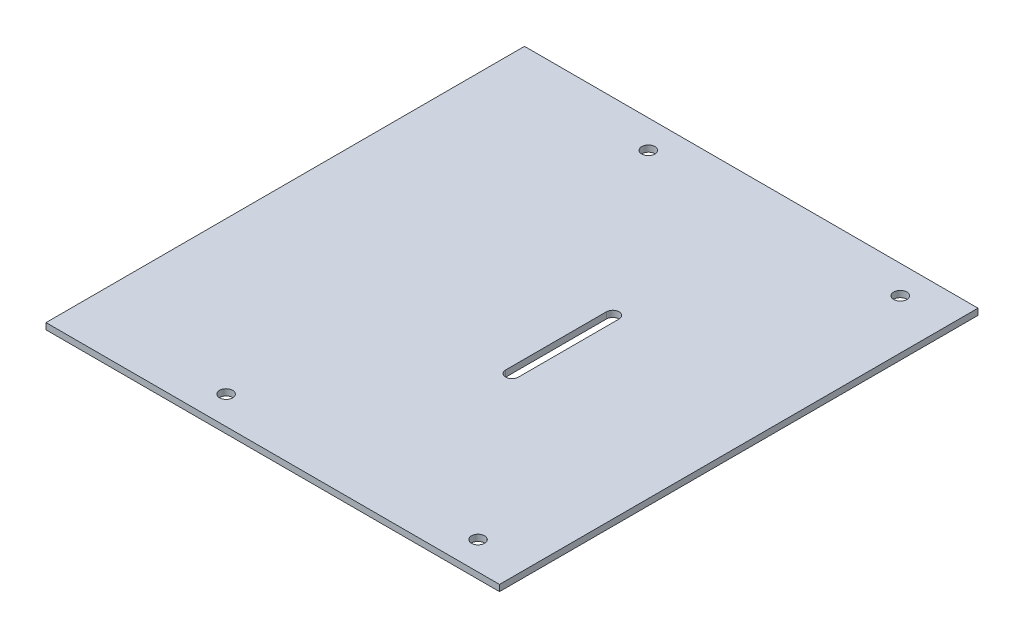
SolidWorks part; units mm, degrees
material "1060 Alloy"
ref_plane "Front Plane" through (0, 0, 0) normal (0, 0, 1) x (1, 0, 0)
ref_plane "Top Plane" through (0, 0, 0) normal (0, 1, 0) x (1, 0, 0)
ref_plane "Right Plane" through (0, 0, 0) normal (1, 0, 0) x (0, 0, -1)
sketch "Sketch1" plane through (0, 0, 0) normal (0, 1, 0) x (1, 0, 0)
  line L0 (361.95, 119.6) -> (-361.95, 119.6) construction
  line L1 (-140.35, -120.6) -> (-368.95, -120.6)
  line L2 (-140.35, -120.6) -> (-140.35, 120.6)
  line L3 (-140.35, 120.6) -> (-368.95, 120.6)
  line L4 (-368.95, -120.6) -> (-368.95, 120.6)
  line L5 (0, -3.8154) -> (0, 119.6) construction
  line L6 (361.3726, 120.6) -> (-361.3726, 120.6) construction
  line L7 (361.3726, -120.6) -> (-361.3726, -120.6) construction
  point P0 (0, 0)
  point P7 (-140.35, 0)
  dimension "D2" = 737.9
  dimension "D3" = 228.6
  dimension "D1" = 241.2
extrude "Boss-Extrude1" add sketch "Sketch1" along normal mid plane 3.175
hole_wizard "M6 Clearance Hole1" positions "Sketch8" profile "Sketch3" hole size "M6" standard "ANSI Metric" end condition through all
sketch "Sketch8" plane through (0, 1.5875, 0) normal (0, 1, 0) x (1, 0, 0)
  line L0 (-165.35, 106.425) -> (-165.35, -106.425) construction
  line L1 (-165.35, -106.425) -> (-292.35, -106.425) construction
  line L3 (-140.35, -120.6) -> (-140.35, 120.6) construction
  point P0 (-292.35, 106.425)
  point P2 (-165.35, 106.425)
  point P4 (-165.35, -106.425)
  point P6 (-292.35, -106.425)
  point P15 (-165.35, 0)
  dimension "D1" = 212.85
  dimension "D2" = 25
  dimension "D3" = 127
sketch "Sketch3" plane through (-292.35, 1.5875, -106.425) normal (1, 0, 0) x (0, 0, 1)
  line L0 (0, 0) -> (0, 3.175)
  line L1 (0, 3.175) -> (3.3, 3.175)
  line L2 (3.3, 3.175) -> (3.3, 0)
  line L5 (3.3, 0) -> (0, 0)
  line L11 (0, -6.35) -> (0, 107.95) construction
  dimension "Thru Hole Dia." = 6.6
  dimension "Thru Hole Depth" = 3.175
sketch "Sketch5" plane through (0, -1.5875, 0) normal (0, -1, 0) x (1, 0, 0)
  line L0 (-175.95, -92.25) -> (-368.95, -92.25)
  line L3 (-368.95, 92.25) -> (-175.95, 92.25)
  line L5 (-368.95, 120.6) -> (-140.35, 120.6) construction
  line L12 (-368.95, -120.6) -> (-368.95, 120.6) construction
  line L16 (-175.95, 92.25) -> (-175.95, -92.25)
  circle A0 centre (-165.35, 106.425) radius 3.3 construction
  circle A1 centre (-165.35, -106.425) radius 3.3 construction
  dimension "D1" = 14.175
  dimension "D2" = 14.175
  dimension "D3" = 14.175
  dimension "D4" = 193
split "Split1" [suppressed] bodies to split 102
sketch "Sketch6" [suppressed] plane through (0, 1.5875, 0) normal (0, 1, 0) x (1, 0, 0)
  line L0 (-140.35, 120.6) -> (-368.95, 120.6) construction
  line L1 (-217.15, -62.5) -> (-292.15, -62.5)
  line L2 (-217.15, -62.5) -> (-217.15, 62.5)
  line L3 (-217.15, 62.5) -> (-292.15, 62.5)
  line L4 (-292.15, -62.5) -> (-292.15, 62.5)
  line L5 (-217.15, -62.5) -> (-292.15, 62.5) construction
  line L6 (-217.15, 62.5) -> (-292.15, -62.5) construction
  point P0 (-254.65, 0)
  point P10 (-254.65, 120.6)
  dimension "D1" = 125
  dimension "D2" = 75
split "Split2" [suppressed] bodies to split 103 104
sketch "Sketch7" plane through (0, 1.5875, 0) normal (0, 1, 0) x (1, 0, 0)
  line L0 (-229.25, -25.4) -> (-229.25, 25.4) construction
  line L1 (-232.425, -25.4) -> (-232.425, 25.4)
  line L2 (-226.075, -25.4) -> (-226.075, 25.4)
  line L5 (-140.35, -120.6) -> (-140.35, 120.6) construction
  arc A0 (-232.425, -25.4) -> (-226.075, -25.4) centre (-229.25, -25.4) ccw
  arc A1 (-226.075, 25.4) -> (-232.425, 25.4) centre (-229.25, 25.4) ccw
  point P2 (-229.25, 0)
  dimension "D1" = 3.175
  dimension "D2" = 50.8
  dimension "D3" = 88.9
extrude "Cut-Extrude1" [suppressed] cut sketch "Sketch7" against normal up to next
sketch "Sketch9" plane through (0, 1.5875, 0) normal (0, 1, 0) x (1, 0, 0)
  line L2 (-226.075, -25.4) -> (-226.075, 25.4)
  line L3 (-232.425, 25.4) -> (-232.425, -25.4)
  line L4 (-226.075, -25.4) -> (-226.075, 25.4)
  line L5 (-232.425, 25.4) -> (-232.425, -25.4)
  arc A2 (-232.425, -25.4) -> (-226.075, -25.4) centre (-229.25, -25.4) ccw
  arc A3 (-226.075, 25.4) -> (-232.425, 25.4) centre (-229.25, 25.4) ccw
  arc A4 (-232.425, -25.4) -> (-226.075, -25.4) centre (-229.25, -25.4) ccw
  arc A5 (-226.075, 25.4) -> (-232.425, 25.4) centre (-229.25, 25.4) ccw
  dimension "D1" = 0
extrude "Cut-Extrude2" cut sketch "Sketch9" against normal through all both and the other way through all
equation "\"Length\"= 28.5in"
equation "\"D2@Sketch1\"=\"Length\"+7*2mm"
equation "\"D2@Sketch5\"=\"D1@Sketch5\""
equation "\"D3@Sketch5\"=\"D2@Sketch5\""
